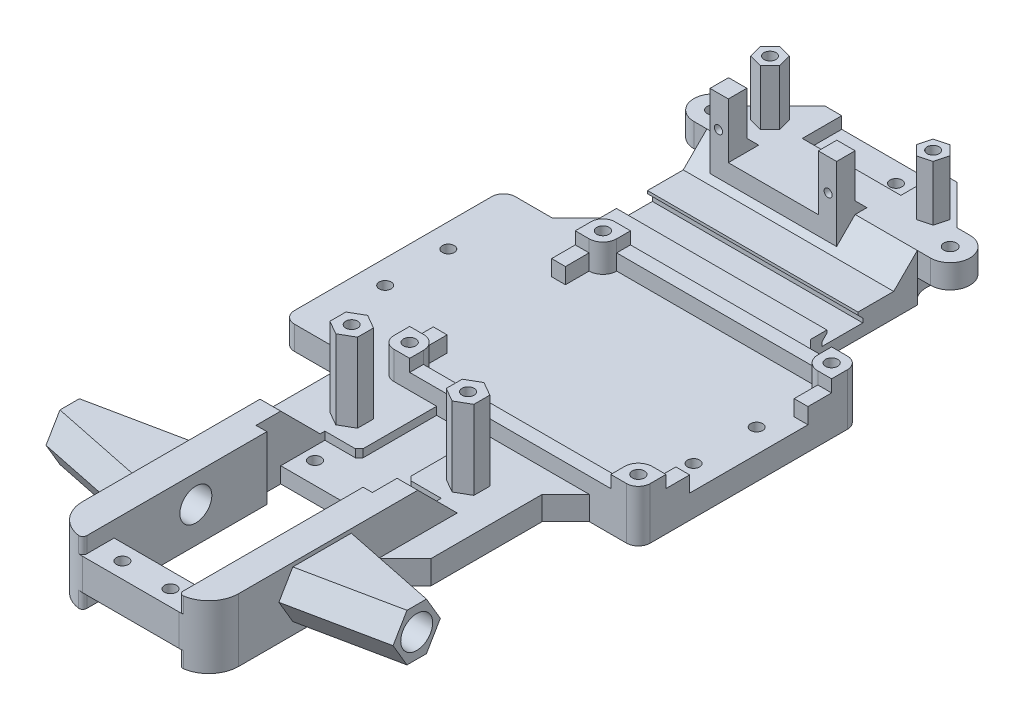
SolidWorks part; units mm, degrees
ref_plane "Front Plane" through (0, 0, 0) normal (0, 0, 1) x (1, 0, 0)
ref_plane "Top Plane" through (0, 0, 0) normal (0, 1, 0) x (1, 0, 0)
ref_plane "Right Plane" through (0, 0, 0) normal (1, 0, 0) x (0, 0, -1)
sketch "Sketch1" plane through (0, 0, 0) normal (0, 1, 0) x (1, 0, 0)
  line L0 (-30, 0) -> (30, 0) construction
  line L1 (-30, 5) -> (30, 5)
  line L2 (-30, -5) -> (30, -5)
  arc A0 (-30, 5) -> (-30, -5) centre (-30, 0) ccw
  arc A1 (30, -5) -> (30, 5) centre (30, 0) ccw
  circle A2 centre (-30, 0) radius 1.6
  circle A3 centre (30, 0) radius 1.6
  point P3 (0, 0)
  dimension "D3" = 3.2
  dimension "D4" = 3.2
  dimension "D1" = 60
  dimension "D2" = 10
extrude "Boss-Extrude1" add sketch "Sketch1" along normal blind 6
sketch "Sketch2" plane through (0, 0, 0) normal (0, -1, 0) x (1, 0, 0)
  line L0 (26.6834, 5) -> (-26.6834, 5)
  line L2 (-26.6834, -5) -> (26.6834, -5)
  arc A0 (-26.6834, -5) -> (-26.6834, 5) centre (-30, 0) ccw
  arc A1 (26.6834, 5) -> (26.6834, -5) centre (30, 0) ccw
  dimension "D1" = 12
  dimension "D2" = 12
extrude "Boss-Extrude2" add sketch "Sketch2" along normal blind 6
sketch "Sketch3" plane through (0, 0, 5) normal (0, 0, 1) x (1, 0, 0)
  line L1 (-26.6834, -6) -> (26.6834, -6)
  line L2 (-26.6834, -6) -> (-26.6834, 0)
  line L3 (-26.6834, 0) -> (26.6834, 0)
  line L4 (26.6834, -6) -> (26.6834, 0)
extrude "Boss-Extrude3" add sketch "Sketch3" along normal blind 120
sketch "Sketch6" plane through (-26.6834, 0, 0) normal (-1, 0, 0) x (0, 0, 1)
  line L6 (27.0663, 0.16) -> (20.9337, 0.16)
  line L7 (20.9337, 0.16) -> (18.84, -1.9337)
  line L8 (18.84, -1.9337) -> (18.84, -3.0013)
  line L10 (29.16, -3.0013) -> (29.16, -1.9337)
  line L11 (29.16, -1.9337) -> (27.0663, 0.16)
  line L13 (18.84, -3.0013) -> (29.16, -3.0013)
  dimension "D1" = 15.9337
extrude "Cut-Extrude1" cut sketch "Sketch6" against normal blind 58
chamfer "Chamfer1" distance 1 angle 45 2 edges at (0, 0, 27.2263) (0, 0, 20.7737) first distance on face at (0, -0.9669, 28.1931) first distance on face at (0, -0.9669, 19.8069)
sketch "Sketch7" plane through (0, 0, 0) normal (0, 1, 0) x (1, 0, 0)
  line L0 (30, 5) -> (-30, 5) construction
  line L1 (-21.2, 5) -> (10.9, 5)
  line L2 (-21.2, 5) -> (-21.2, -9.7)
  line L3 (-21.2, -9.7) -> (10.9, -9.7)
  line L4 (10.9, 5) -> (10.9, -9.7)
  line L5 (26.6834, -5) -> (-26.6834, -5) construction
  line L6 (-21.2, -9.7) -> (-16.5587, -9.7)
  line L7 (-21.2, -9.7) -> (-21.2, -5)
  line L8 (-21.2, -5) -> (-16.5587, -5)
  line L9 (-16.5587, -9.7) -> (-16.5587, -5)
  line L11 (10.9, -9.7) -> (6.2587, -9.7)
  line L12 (10.9, -9.7) -> (10.9, -5)
  line L13 (10.9, -5) -> (6.2587, -5)
  line L14 (6.2587, -9.7) -> (6.2587, -5)
  point P6 (0, -9.7)
  point P16 (-5.15, -9.7)
  line M10 (26.6834, -5) -> (-26.6834, -5)
  dimension "D1" = 10.9
  dimension "D2" = 32.1
  dimension "D3" = 14.7
  dimension "D4" = 22.8175
  dimension "D5" = 11.4087
extrude "Boss-Extrude5" add sketch "Sketch7" along normal blind 20 contours L3 L9 L2 M10 | L14 L3 L4 M10 region at (-18.8794, 0, 7.35) region at (8.5794, 0, 7.35)
sketch "Sketch8" plane through (0, 0, 5) normal (0, 0, 1) x (1, 0, 0)
  line L4 (-16.5587, 0) -> (6.2587, 0)
  line L5 (6.2587, 0) -> (6.2587, 6)
  line L6 (6.2587, 6) -> (-16.5587, 6)
  line L7 (-16.5587, 6) -> (-16.5587, 0)
  line L8 (-16.5587, 0) -> (6.2587, 0)
  line L9 (6.2587, 0) -> (6.2587, 6)
  line L10 (6.2587, 6) -> (-16.5587, 6)
  line L11 (-16.5587, 6) -> (-16.5587, 0)
  dimension "D1" = 0
extrude "Boss-Extrude6" add sketch "Sketch8" along normal up to surface (4.7 mm away) up to face at (-18.8794, 10, 9.7)
sketch "Sketch9" plane through (0, 0, 9.7) normal (0, 0, 1) x (1, 0, 0)
  line L0 (-21.2, 20) -> (-21.2, 0) construction
  line L3 (10.9, 20) -> (10.9, 0) construction
  line L5 (-21.2, 0) -> (10.9, 0) construction
  circle A0 centre (-19.05, 12) radius 1.025
  circle A1 centre (8.75, 12) radius 1.025
  dimension "D2" = 2.05
  dimension "D6" = 2.05
  dimension "D1" = 2.15
  dimension "D3" = 12
  dimension "D5" = 2.15
extrude "Cut-Extrude2" cut sketch "Sketch9" against normal blind 18
sketch "Sketch12" plane through (0, 0, 0) normal (0, 1, 0) x (1, 0, 0)
  line L0 (26.6834, -29.16) -> (-26.6834, -29.16) construction
  line L1 (-45.1, -94.16) -> (-45.1, -38.16)
  line L2 (-45.1, -94.16) -> (45.1, -94.16)
  line L3 (45.1, -94.16) -> (45.1, -38.16)
  line L4 (-45.1, -38.16) -> (45.1, -38.16)
  dimension "D1" = 90.2
  dimension "D2" = 56
  dimension "D3" = 9
extrude "Boss-Extrude11" add sketch "Sketch12" against normal through all
sketch "Sketch16" plane through (0, 0, 0) normal (0, 1, 0) x (1, 0, 0)
  line L0 (26.6834, -94.16) -> (45.1, -94.16) construction
  line L1 (-6.05, -125) -> (6.05, -125)
  line L2 (-6.05, -125) -> (-6.05, -94.16)
  line L3 (-6.05, -94.16) -> (6.05, -94.16)
  line L4 (6.05, -125) -> (6.05, -94.16)
  line L5 (26.6834, -125) -> (-26.6834, -125) construction
  line L6 (-6.05, -125) -> (-14.75, -125)
  line L7 (-14.55, -125) -> (14.55, -125)
  line L8 (-14.55, -125) -> (-14.55, -114)
  line L9 (-14.55, -114) -> (14.55, -114)
  line L10 (14.55, -125) -> (14.55, -114)
  line L11 (-6.05, -125) -> (-6.05, -113.8)
  line L12 (-6.05, -113.8) -> (-14.75, -113.8)
  line L13 (-14.75, -125) -> (-14.75, -113.8)
  line L14 (6.05, -125) -> (14.75, -125)
  line L15 (6.05, -125) -> (6.05, -113.8)
  line L16 (6.05, -113.8) -> (14.75, -113.8)
  line L17 (14.75, -125) -> (14.75, -113.8)
  circle A0 centre (-11.55, -119.5) radius 1.55
  circle A1 centre (11.55, -119.5) radius 1.55
  point P6 (0, -125)
  point P7 (0, -125)
  line M13 (-26.6834, -125) -> (26.6834, -125)
  dimension "D7" = 3.1
  dimension "D9" = 3.1
  dimension "D1" = 12.1
  dimension "D2" = 8.5
  dimension "D3" = 8.5
  dimension "D4" = 11
  dimension "D5" = 3
  dimension "D6" = 5.5
  dimension "D8" = 3
  dimension "D11" = 0.2
  dimension "D12" = 0.2
  dimension "D13" = 0.2
  dimension "D14" = 0.2
extrude "Cut-Extrude3" cut sketch "Sketch16" against normal blind 13.1 contours A0 | A1 region at (-11.55, 0, 119.5) region at (11.55, 0, 119.5)
sketch "Sketch17" plane through (0, 0, 0) normal (0, 1, 0) x (1, 0, 0)
  line L0 (41.6, -45.16) -> (41.6, -87.16)
  line L5 (26.6834, -94.16) -> (45.1, -94.16) construction
  line L8 (45.1, -94.16) -> (45.1, -38.16) construction
  line L9 (-12.9, -41.66) -> (38.1, -41.66)
  line L10 (-19.9, -38.16) -> (45.1, -38.16)
  line L11 (-19.9, -38.16) -> (-19.9, -94.16)
  line L12 (-19.9, -94.16) -> (45.1, -94.16)
  line L13 (45.1, -38.16) -> (45.1, -94.16)
  line L14 (-16.4, -45.16) -> (-16.4, -87.16)
  line L15 (-12.9, -90.66) -> (38.1, -90.66)
  circle A0 centre (-16.4, -41.66) radius 1.55
  circle A1 centre (41.6, -41.66) radius 1.55
  circle A2 centre (41.6, -90.66) radius 1.55
  circle A3 centre (-16.4, -90.66) radius 1.55
  arc A5 (38.1, -41.66) -> (41.6, -45.16) centre (41.6, -41.66) ccw
  arc A6 (41.6, -87.16) -> (38.1, -90.66) centre (41.6, -90.66) ccw
  arc A7 (-12.9, -90.66) -> (-16.4, -87.16) centre (-16.4, -90.66) ccw
  arc A8 (-16.4, -45.16) -> (-12.9, -41.66) centre (-16.4, -41.66) ccw
  dimension "D5" = 3.1
  dimension "D10" = 3.5
  dimension "D11" = 3.5
  dimension "D12" = 3.5
  dimension "D13" = 3.5
  dimension "D1" = 3.5
  dimension "D2" = 3.5
  dimension "D3" = 3.5
  dimension "D4" = 3.5
  dimension "D6" = 3.5
  dimension "D7" = 3.5
  dimension "D8" = 3.5
  dimension "D9" = 3.5
  dimension "D14" = 42
  dimension "D15" = 51
  dimension "D16" = 2
  dimension "D18" = 3.5
  dimension "D17" = 2
extrude "Boss-Extrude12" add sketch "Sketch17" along normal blind 4
sketch "Sketch18" plane through (0, 4, 0) normal (0, 1, 0) x (1, 0, 0)
  line L4 (-16.4, -45.16) -> (-19.9, -45.16)
  line L11 (-19.9, -38.16) -> (-19.9, -94.16) construction
  line L12 (-19.9, -45.16) -> (-19.9, -38.16)
  line L13 (-19.9, -38.16) -> (-12.9, -38.16)
  line L22 (26.6834, -38.16) -> (-19.9, -38.16) construction
  line L23 (-12.9, -38.16) -> (-12.9, -41.66)
  line L24 (-16.4, -87.16) -> (-19.9, -87.16)
  line L25 (-19.9, -38.16) -> (-19.9, -94.16) construction
  line L26 (-19.9, -87.16) -> (-19.9, -94.16)
  line L27 (-19.9, -94.16) -> (-12.9, -94.16)
  line L28 (-19.9, -94.16) -> (26.6834, -94.16) construction
  line L29 (-12.9, -94.16) -> (-12.9, -90.66)
  line L30 (12.6, -41.66) -> (12.6, -90.66) construction
  line L31 (38.1, -41.66) -> (-12.9, -41.66) construction
  line L32 (-12.9, -90.66) -> (38.1, -90.66) construction
  line L33 (38.1, -94.16) -> (38.1, -90.66)
  line L34 (45.1, -94.16) -> (38.1, -94.16)
  line L35 (45.1, -87.16) -> (45.1, -94.16)
  line L36 (41.6, -87.16) -> (45.1, -87.16)
  line L37 (38.1, -38.16) -> (38.1, -41.66)
  line L38 (45.1, -38.16) -> (38.1, -38.16)
  line L39 (45.1, -45.16) -> (45.1, -38.16)
  line L40 (41.6, -45.16) -> (45.1, -45.16)
  circle A10 centre (-16.4, -41.66) radius 1.55
  arc A11 (-16.4, -45.16) -> (-12.9, -41.66) centre (-16.4, -41.66) ccw
  circle A12 centre (-16.4, -90.66) radius 1.55
  arc A13 (-12.9, -90.66) -> (-16.4, -87.16) centre (-16.4, -90.66) ccw
  arc A14 (38.1, -90.66) -> (41.6, -87.16) centre (41.6, -90.66) cw
  circle A15 centre (41.6, -90.66) radius 1.55
  arc A16 (41.6, -45.16) -> (38.1, -41.66) centre (41.6, -41.66) cw
  circle A17 centre (41.6, -41.66) radius 1.55
extrude "Boss-Extrude13" add sketch "Sketch18" along normal blind 3.1
extrude "Cut-Extrude4" cut sketch "Sketch16<3>" against normal blind 2 contours L9 L8 L2 A0 M13 | L9 L2 L4 M13 | L2 L9 L4 L3 | L10 L9 L4 A1 M13 | L13 L8 L9 L2 L12 M13 | L17 L16 L4 L9 L10 M13 | L4 L3 L2 L1 region at (0, 0, 119.5) region at (-10.3, 0, 124.861) region at (6.189, 0, 119.5) region at (-10.3, 0, 113.8582) region at (0, 0, 104.08) region at (6.1918, 0, 113.9)
sketch "Sketch16<3>" plane through (0, 0, 0) normal (0, 1, 0) x (1, 0, 0) same geometry as "Sketch16"
sketch "Sketch19" plane through (0, 0, 0) normal (0, 1, 0) x (1, 0, 0)
  line L5 (26.6834, -125) -> (14.75, -125) construction
  line L6 (-14.75, -125) -> (-20, -125)
  line L7 (-12, -131.2622) -> (-12, -170)
  line L8 (12, -170) -> (-12, -170)
  line L9 (20, -125) -> (20, -178)
  line L10 (20, -125) -> (14.75, -125)
  line L11 (-20, -125) -> (-20, -178)
  line L12 (20, -178) -> (-20, -178)
  line L13 (12.4, -131.2622) -> (12.4, -170)
  line L14 (12, -170) -> (12.4, -170)
  line L17 (-12, -131.2622) -> (-14.75, -131.2622)
  line L18 (-14.75, -125) -> (-14.75, -131.2622)
  line L21 (12.4, -131.2622) -> (14.75, -131.2622)
  line L22 (14.75, -125) -> (14.75, -131.2622)
  dimension "D1" = 24
  dimension "D2" = 8
  dimension "D3" = 0.4
  dimension "D4" = 53
  dimension "D5" = 12
  dimension "D6" = 8
  dimension "D7" = 7.6
  dimension "D8" = 2.35
extrude "Boss-Extrude15" add sketch "Sketch19" along normal blind 10 and the other way through all
chamfer "Chamfer2" distance 10 angle 45 2 edges at (20, -3, 125) (-20, -3, 125)
chamfer "Chamfer3" distance 10 angle 45 2 edges at (-17.375, 0, 125) (17.375, 0, 125)
sketch "Sketch20" plane through (-20, 0, 0) normal (-1, 0, 0) x (0, 0, 1)
  line L0 (125, 10) -> (178, 10) construction
  line L1 (178, -6) -> (178, 10) construction
  circle A0 centre (149.27, 3) radius 4.05
  dimension "D3" = 8.1
  dimension "D1" = 7
  dimension "D2" = 28.73
extrude "Cut-Extrude5" cut sketch "Sketch20" against normal blind 47
sketch "Sketch21" plane through (12.4, 0, 0) normal (-1, 0, 0) x (0, 0, 1)
  circle A0 centre (149.27, 3) radius 4.05
  circle A1 centre (149.27, 3) radius 6
  circle A2 centre (149.27, 3) radius 4.05 construction
  dimension "D2" = 12
extrude "Boss-Extrude16" add sketch "Sketch21" along normal blind 0.4
sketch "Sketch26" plane through (-20, 0, 0) normal (-1, 0, 0) x (0, 0, 1)
  line L1 (143.27, -3) -> (155.27, -3)
  line L2 (143.27, -3) -> (143.27, 9)
  line L3 (143.27, 9) -> (155.27, 9)
  line L4 (155.27, -3) -> (155.27, 9)
  line L5 (143.27, -3) -> (155.27, 9) construction
  line L6 (143.27, 9) -> (155.27, -3) construction
  point P0 (149.27, 3)
  dimension "D1" = 12
  dimension "D2" = 12
extrude "Boss-Extrude17" add sketch "Sketch26" along normal blind 24
chamfer "Chamfer5" distance 4.95 distance2 24 2 edges at (-20, 3, 143.27) (-20, 3, 155.27) first distance on face at (-20, 1.3333, 144.3333)
chamfer "Chamfer6" distance 6 angle 30 4 edges at (-32, 9, 157.745) (-32, -3, 157.745) (-32, -3, 140.795) (-32, 9, 140.795) first distance on face at (-32, 3, 157.745) first distance on face at (-32, 3, 140.795)
mirror "Mirror19" about plane through (0, 0, 0) normal (1, 0, 0) of "Boss-Extrude17", "Cut-Extrude5"
chamfer "Chamfer8" distance 24 distance2 4.95 2 edges at (20, 3, 143.27) (20, 3, 155.27) first distance on face at (32, 3, 143.27) first distance on face at (32, 3, 155.27)
chamfer "Chamfer9" distance 6 angle 30 4 edges at (32, 9, 140.795) (32, -3, 140.795) (32, -3, 157.745) (32, 9, 157.745) first distance on face at (32, 3, 140.795) first distance on face at (32, 3, 157.745)
sketch "Sketch28" plane through (-27, 0, 0) normal (1, 0, 0) x (0, 0, -1)
  circle A0 centre (-149.27, 3) radius 4.05
  dimension "D1" = 8.1
extrude "Cut-Extrude8" cut sketch "Sketch28" against normal blind 24 and the other way blind 76
extrude "Cut-Extrude9" cut sketch "Sketch17<2>" against normal blind 9 contours A0 | A1 | A2 | A3 region at (-16.4, 0, 41.66) region at (41.6, 0, 41.66) region at (41.6, 0, 90.66) region at (-16.4, 0, 90.66)
sketch "Sketch17<2>" plane through (0, 0, 0) normal (0, 1, 0) x (1, 0, 0) same geometry as "Sketch17"
chamfer "Chamfer10" distance 6 angle 45 4 edges at (26.6834, -3, 94.16) (26.6834, -3, 38.16) (-26.6834, -3, 38.16) (-26.6834, -3, 94.16)
fillet "Fillet2" radius 3 6 edges at (45.1, 0.55, 94.16) (45.1, 0.55, 38.16) (-45.1, -3, 94.16) (-45.1, -3, 38.16) (-19.9, 3.55, 38.16) (-19.9, 3.55, 94.16)
chamfer "Chamfer11" distance 1 angle 45 2 edges at (6.05, -1, 113.8) (-6.05, -1, 113.8)
chamfer "Chamfer12" distance 3 angle 45 2 edges at (-18.8794, 6, 5) (8.5794, 6, 5)
fillet "Fillet3" radius 8 1 edges at (-20, 2, 178)
sketch "Sketch29" plane through (-45.1, 0, 0) normal (-1, 0, 0) x (0, 0, 1)
  line L0 (45.16, 4) -> (87.16, 4) construction
  line L1 (51.16, 4) -> (81.16, 4)
  line L2 (51.16, 4) -> (51.16, 0)
  line L3 (51.16, 0) -> (81.16, 0)
  line L4 (81.16, 4) -> (81.16, 0)
  line L5 (41.16, 0) -> (41.16, -6) construction
  dimension "D1" = 30
  dimension "D2" = 10
extrude "Cut-Extrude10" cut sketch "Sketch29" against normal blind 97
sketch "Sketch30" plane through (0, 0, 0) normal (0, 1, 0) x (1, 0, 0)
  line L1 (-45.1, -51.16) -> (-33.1, -51.16)
  line L2 (-45.1, -51.16) -> (-45.1, -81.16)
  line L3 (-45.1, -81.16) -> (-33.1, -81.16)
  line L4 (-33.1, -51.16) -> (-33.1, -81.16)
  circle A0 centre (-39.1, -58.16) radius 1.525
  circle A1 centre (-39.1, -74.16) radius 1.525
  point P10 (-39.1, -51.16)
  dimension "D4" = 3.05
  dimension "D5" = 3.05
  dimension "D1" = 12
  dimension "D2" = 7
  dimension "D3" = 7
extrude "Cut-Extrude11" cut sketch "Sketch30" against normal blind 9 contours A0 | A1
mirror "Mirror20" about plane through (0, 0, 0) normal (1, 0, 0) of "Cut-Extrude11"
sketch "Sketch32" plane through (0, -6, 0) normal (0, -1, 0) x (1, 0, 0)
  line L1 (-26.6834, -5) -> (26.6834, -5)
  line L2 (-26.6834, -5) -> (-26.6834, -15)
  line L3 (-26.6834, -15) -> (26.6834, -15)
  line L4 (26.6834, -5) -> (26.6834, -15)
  dimension "D1" = 10
extrude "Boss-Extrude18" add sketch "Sketch32" against normal up to surface (12 mm away) up to face at (-30, 6, 1.6)
chamfer "Chamfer13" distance 10 angle 45 2 edges at (-26.6834, 0, -15) (26.6834, 0, -15)
chamfer "Chamfer14" distance 6 angle 45 1 edges at (-23.9417, 0, 5)
sketch "Sketch33" plane through (0, 0, -15) normal (0, 0, -1) x (-1, 0, 0)
  line L2 (-12.5, 6) -> (12.5, 6)
  line L3 (-12.5, 6) -> (-12.5, -6)
  line L4 (-12.5, -6) -> (12.5, -6)
  line L5 (12.5, 6) -> (12.5, -6)
  line L6 (16.6834, -6) -> (-16.6834, -6) construction
  line L8 (-12.5, -3) -> (12.5, -3)
  line L9 (-12.5, -3) -> (-12.5, 3)
  line L10 (-12.5, 3) -> (12.5, 3)
  line L11 (12.5, -3) -> (12.5, 3)
  line L12 (-12.5, -3) -> (12.5, 3) construction
  line L13 (-12.5, 3) -> (12.5, -3) construction
  point P0 (0, 6)
  point P1 (0, 0)
  line M7 (-16.6834, -6) -> (16.6834, -6)
  line M9 (16.6834, 6) -> (-16.6834, 6)
  dimension "D1" = 25
  dimension "D2" = 6
extrude "Cut-Extrude12" cut sketch "Sketch33" against normal blind 10 contours L8 L3 L5 M7 | L3 L10 L5 M9 region at (0, 4.5, -15) region at (0, -4.5, -15)
sketch "Sketch34" plane through (0, 3, 0) normal (0, 1, 0) x (1, 0, 0)
  line L0 (-12.5, 5) -> (12.5, 5) construction
  circle A0 centre (-6.25, 10) radius 1.525
  circle A1 centre (6.25, 10) radius 1.525
  dimension "D1" = 3.05
  dimension "D3" = 3.05
  dimension "D2" = 6.25
  dimension "D4" = 12.5
  dimension "D5" = 5
extrude "Cut-Extrude13" cut sketch "Sketch34" against normal blind 10
sketch "Sketch38" plane through (0, 6, 0) normal (0, 1, 0) x (1, 0, 0)
  line L3 (0, 0) -> (0, 19.8308) construction
  line L36 (-16.6834, 15) -> (-26.6834, 5) construction
  line L37 (-17.3373, 4.1034) -> (-18.2339, 7.4495)
  line L38 (-18.2339, 7.4495) -> (-21.58, 8.3461)
  line L39 (-21.58, 8.3461) -> (-24.0294, 5.8966)
  line L40 (-24.0294, 5.8966) -> (-23.1329, 2.5505)
  line L41 (-23.1329, 2.5505) -> (-19.7868, 1.6539)
  line L42 (-19.7868, 1.6539) -> (-17.3373, 4.1034)
  line L43 (19.7868, 1.6539) -> (17.3373, 4.1034)
  line L44 (23.1329, 2.5505) -> (19.7868, 1.6539)
  line L45 (24.0294, 5.8966) -> (23.1329, 2.5505)
  line L46 (21.58, 8.3461) -> (24.0294, 5.8966)
  line L47 (18.2339, 7.4495) -> (21.58, 8.3461)
  line L48 (17.3373, 4.1034) -> (18.2339, 7.4495)
  circle A0 centre (-20.6834, 5) radius 1.525
  circle A2 centre (-20.6834, 5) radius 3 construction
  circle A5 centre (20.6834, 5) radius 3 construction
  circle A6 centre (20.6834, 5) radius 1.525
  dimension "D1" = 3.05
  dimension "D2" = 6
  dimension "D3" = 6
extrude "Boss-Extrude19" add sketch "Sketch38" along normal up to surface (14 mm away) up to face at (8.5794, 20, 7.35)
sketch "Sketch39" plane through (0, 0, 0) normal (0, 1, 0) x (1, 0, 0)
  line L0 (0, -125) -> (0, -92.1072) construction
  line L1 (-14.75, -102.9585) -> (-18.25, -104.9793)
  line L2 (-18.25, -104.9793) -> (-18.25, -109.0207)
  line L3 (-18.25, -109.0207) -> (-14.75, -111.0415)
  line L4 (-14.75, -111.0415) -> (-11.25, -109.0207)
  line L5 (-11.25, -109.0207) -> (-11.25, -104.9793)
  line L6 (-11.25, -104.9793) -> (-14.75, -102.9585)
  line L13 (-14.75, -125) -> (14.75, -125) construction
  line L14 (11.25, -104.9793) -> (14.75, -102.9585)
  line L15 (11.25, -109.0207) -> (11.25, -104.9793)
  line L16 (14.75, -111.0415) -> (11.25, -109.0207)
  line L17 (18.25, -109.0207) -> (14.75, -111.0415)
  line L18 (18.25, -104.9793) -> (18.25, -109.0207)
  line L19 (14.75, -102.9585) -> (18.25, -104.9793)
  circle A0 centre (-14.75, -107) radius 1.525
  circle A2 centre (-14.75, -107) radius 3.5 construction
  circle A3 centre (14.75, -107) radius 3.5 construction
  circle A4 centre (14.75, -107) radius 1.525
  dimension "D1" = 3.05
  dimension "D4" = 7
  dimension "D5" = 5.25
  dimension "D6" = 28
extrude "Boss-Extrude20" add sketch "Sketch39" along normal up to surface (20 mm away) up to face at (-18.8794, 20, 7.35)
sketch "Sketch40" plane through (0, 0, 178) normal (0, 0, 1) x (1, 0, 0)
  line L0 (12.4, -6) -> (12.4, 10) construction
  line L2 (-12, 10) -> (12.4, 10)
  line L3 (-12, 10) -> (-12, -6)
  line L4 (-12, -6) -> (12.4, -6)
  line L5 (12.4, 10) -> (12.4, -6)
  line L6 (-12, -2) -> (12.4, -2)
  line L7 (-12, -2) -> (-12, 6)
  line L8 (-12, 6) -> (12.4, 6)
  line L9 (12.4, -2) -> (12.4, 6)
  line L10 (-12, -2) -> (12.4, 6) construction
  line L11 (-12, 6) -> (12.4, -2) construction
  point P0 (0.2, 2)
  point P12 (-12, 2)
  line M9 (-12, -6) -> (20, -6)
  line M11 (20, 10) -> (-12, 10)
  line M12 (-12, 10) -> (-12, -6)
  dimension "D1" = 8
fillet "Fillet4" radius 7.6 1 edges at (20, 2, 178)
extrude "Cut-Extrude14" cut sketch "Sketch40" against normal blind 10 contours L8 L5 M12 M11 | L6 L3 L5 M9 region at (0.2, 8, 178) region at (0.2, -4, 178)
fillet "Fillet6" radius 1 4 edges at (12.4, 8, 178) (12.4, -4, 178) (-12, -4, 178) (-12, 8, 178)
sketch "Sketch42" plane through (0, 6, 0) normal (0, 1, 0) x (1, 0, 0)
  line L0 (0.2, -178) -> (0.2, -170) construction
  line L2 (-12, -178) -> (12.4, -178) construction
  line L3 (12.4, -170) -> (-12, -170) construction
  circle A0 centre (-5.9, -174) radius 1.525
  circle A1 centre (6.3, -174) radius 1.525
  dimension "D2" = 3.05
  dimension "D1" = 6.1
  dimension "D3" = 4
extrude "Cut-Extrude15" cut sketch "Sketch42" against normal blind 10
